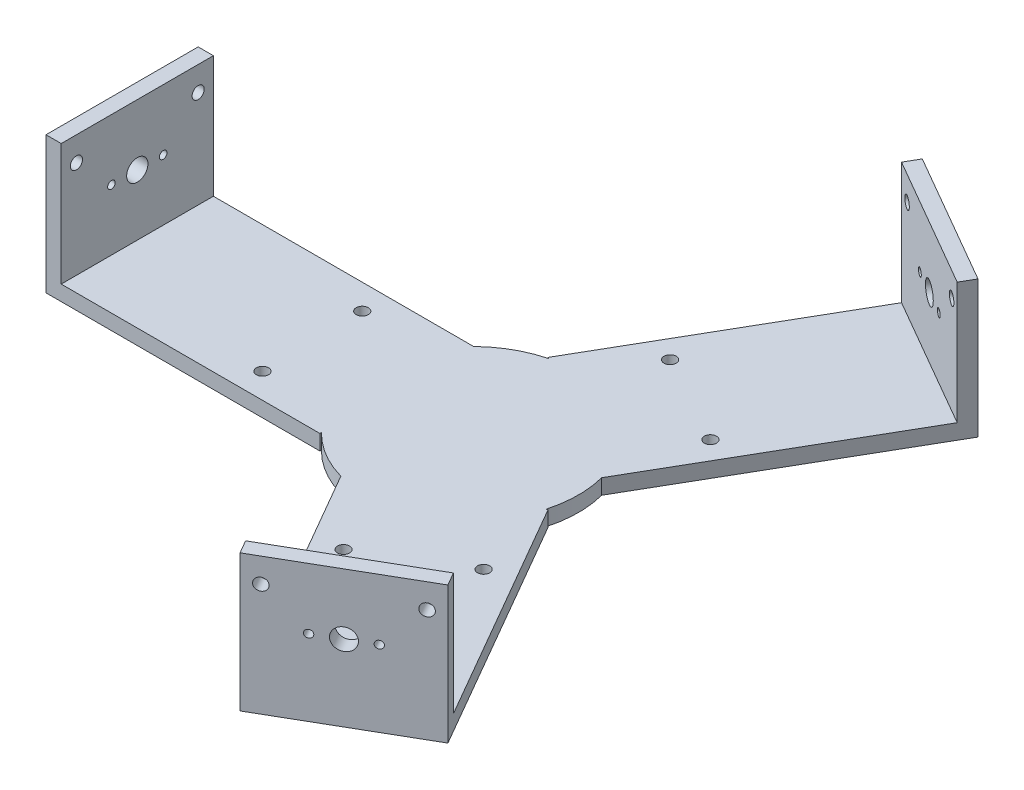
SolidWorks part; units mm, degrees
ref_plane "Plan de face" through (0, 0, 0) normal (0, 0, 1) x (1, 0, 0)
ref_plane "Plan de dessus" through (0, 0, 0) normal (0, 1, 0) x (1, 0, 0)
ref_plane "Plan de droite" through (0, 0, 0) normal (1, 0, 0) x (0, 0, -1)
sketch "Esquisse3" plane through (0, 0, 0) normal (0, 1, 0) x (1, 0, 0)
  line L0 (-150.1573, 0) -> (189.6273, 0) construction
  line L1 (-83.8395, -145.9242) -> (87.7229, 151.2306) construction
  line L2 (-78.0725, 135.2255) -> (117.7517, -203.9519) construction
  line L3 (-125, 131.2995) -> (-125, -153.5705) construction
  line L4 (-25, -25) -> (-115, -25)
  line L6 (-25, 25) -> (-24.4949, 25)
  line L7 (-115, -25) -> (-115, 25)
  line L8 (-25, -25) -> (-115, 25) construction
  line L9 (-25, 25) -> (-115, -25) construction
  line L10 (-24.4949, 25) -> (-115, 25)
  line L11 (33.8981, 8.7132) -> (79.1506, 87.0929)
  line L12 (35.8494, 112.0929) -> (79.1506, 87.0929)
  line L13 (-9.1506, 34.1506) -> (35.8494, 112.0929)
  line L14 (-9.4032, -33.7132) -> (35.8494, -112.0929)
  line L15 (79.1506, -87.0929) -> (35.8494, -112.0929)
  line L16 (34.1506, -9.1506) -> (79.1506, -87.0929)
  line L17 (-24.4949, 25) -> (-25, -25)
  line L18 (-9.1506, 34.1506) -> (33.8981, 8.7132)
  line L19 (-9.4032, -33.7132) -> (34.1506, -9.1506)
  circle A0 centre (0, 0) radius 125
  circle A1 centre (0, 0) radius 35
  circle A2 centre (0, 0) radius 125
  circle A3 centre (0, 0) radius 125
  point P9 (-70, 0)
  point P32 (0, 0)
  dimension "D1" = 250
  dimension "D4" = 70
  dimension "D2" = 120
  dimension "D3" = 120
  dimension "D5" = 10
  dimension "D6" = 50
  dimension "D7" = 90
  dimension "D8" = 3
extrude "Boss.-Extru.3" add sketch "Esquisse3" along normal blind 5 contours A1 L6 L10 L7 L4 L17 | A1 L14 L15 L16 L19 | L19 A1 L18 L17 | A1 L11 L12 L13 L18 | L18 A1 | A1 region at (-73.3157, 0, -0.0007) region at (0, 0, 0) region at (36.6572, 0, 63.4937) region at (14.7041, 0, -24.8843) region at (36.6585, 0, -63.4929)
sketch "Esquisse4" plane through (0, 5, 0) normal (0, 1, 0) x (1, 0, 0)
  line L0 (-25, -25) -> (-115, -25) construction
  line L1 (-115, 25) -> (-110, 25)
  line L2 (-115, 25) -> (-115, -25)
  line L3 (-115, -25) -> (-110, -25)
  line L4 (-110, 25) -> (-110, -25)
  line L5 (35.8494, 112.0929) -> (79.1506, 87.0929)
  line L6 (79.1506, 87.0929) -> (76.6506, 82.7628)
  line L7 (33.8981, 8.7132) -> (79.1506, 87.0929) construction
  line L8 (76.6506, 82.7628) -> (33.3494, 107.7628)
  line L9 (-9.1506, 34.1506) -> (35.8494, 112.0929) construction
  line L10 (33.3494, 107.7628) -> (35.8494, 112.0929)
  line L11 (79.1506, -87.0929) -> (76.6506, -82.7628)
  line L12 (34.1506, -9.1506) -> (79.1506, -87.0929) construction
  line L13 (76.6506, -82.7628) -> (33.3494, -107.7628)
  line L14 (-9.4032, -33.7132) -> (35.8494, -112.0929) construction
  line L15 (33.3494, -107.7628) -> (35.8494, -112.0929)
  line L16 (35.8494, -112.0929) -> (79.1506, -87.0929)
  dimension "D1" = 5
  dimension "D2" = 5
  dimension "D3" = 5
extrude "Boss.-Extru.4" add sketch "Esquisse4" along normal blind 40
sketch "Esquisse5" plane through (-110, 0, 0) normal (1, 0, 0) x (0, 0, -1)
  line L0 (-25, 25) -> (39.5019, 25) construction
  line L1 (-25, 45) -> (-25, 5) construction
  circle A0 centre (0, 25) radius 3.5
  circle A1 centre (-8.5, 25) radius 1.25
  circle A2 centre (8.5, 25) radius 1.25
  dimension "D1" = 7
  dimension "D4" = 2.5
  dimension "D5" = 2.5
  dimension "D2" = 8.5
  dimension "D3" = 8.5
extrude "Enlèv. mat.-Extru.1" cut sketch "Esquisse5" against normal through all
sketch "Esquisse6" plane through (55, 0, 95.2628) normal (-0.5, 0, -0.866) x (-0.866, 0, 0.5)
  line L0 (-25, 25) -> (25, 25) construction
  line L1 (-25, 45) -> (-25, 5) construction
  line L2 (25, 45) -> (25, 5) construction
  circle A0 centre (0, 25) radius 3.5
  circle A1 centre (-8.5, 25) radius 1.25
  circle A2 centre (8.5, 25) radius 1.25
  dimension "D1" = 7
  dimension "D4" = 2.5
  dimension "D5" = 2.5
  dimension "D2" = 8.5
  dimension "D3" = 8.5
extrude "Enlèv. mat.-Extru.2" cut sketch "Esquisse6" against normal through all
sketch "Esquisse7" plane through (55, 0, -95.2628) normal (-0.5, 0, 0.866) x (0.866, 0, 0.5)
  line L0 (-25, 25) -> (25, 25) construction
  line L1 (-25, 45) -> (-25, 5) construction
  line L2 (25, 45) -> (25, 5) construction
  circle A0 centre (0, 25) radius 3.5
  circle A1 centre (8.5, 25) radius 1.25
  circle A2 centre (-8.5, 25) radius 1.25
  dimension "D1" = 7
  dimension "D4" = 2.5
  dimension "D5" = 2.5
  dimension "D2" = 8.5
  dimension "D3" = 8.5
extrude "Enlèv. mat.-Extru.3" cut sketch "Esquisse7" against normal through all
sketch "Esquisse8" plane through (0, 5, 0) normal (0, 1, 0) x (1, 0, 0)
  circle A0 centre (11.9158, -54.1387) radius 2 construction
  circle A1 centre (40.5685, -36.7667) radius 2 construction
  circle A2 centre (11.5566, 53.5167) radius 2 construction
  circle A3 centre (40.9276, 37.3887) radius 2 construction
  circle A4 centre (-52.1251, -16.75) radius 2 construction
  circle A5 centre (-52.8434, 16.75) radius 2 construction
  circle A6 centre (11.9158, -54.1387) radius 2
  circle A7 centre (40.5685, -36.7667) radius 2
  circle A8 centre (11.5566, 53.5167) radius 2
  circle A9 centre (40.9276, 37.3887) radius 2
  circle A10 centre (-52.1251, -16.75) radius 2
  circle A11 centre (-52.8434, 16.75) radius 2
extrude "Enlèv. mat.-Extru.4" cut sketch "Esquisse8" against normal through all
sketch "Esquisse9" plane through (-115, 0, 0) normal (-1, 0, 0) x (0, 0, 1)
  circle A0 centre (-20, 37) radius 2 construction
  circle A1 centre (20, 37) radius 2 construction
  circle A2 centre (-20, 37) radius 2
  circle A3 centre (20, 37) radius 2
sketch "Esquisse10" plane through (57.5, 0, -99.5929) normal (0.5, 0, -0.866) x (-0.866, 0, -0.5)
  circle A0 centre (-20, 37) radius 2 construction
  circle A1 centre (20, 37) radius 2 construction
  circle A2 centre (-20, 37) radius 2
  circle A3 centre (20, 37) radius 2
sketch "Esquisse11" plane through (57.5, 0, 99.5929) normal (0.5, 0, 0.866) x (0.866, 0, -0.5)
  circle A0 centre (20, 37) radius 2 construction
  circle A1 centre (-20, 37) radius 2 construction
  circle A2 centre (20, 37) radius 2
  circle A3 centre (-20, 37) radius 2
extrude "Enlèv. mat.-Extru.5" cut sketch "Esquisse9" against normal through all
extrude "Enlèv. mat.-Extru.6" cut sketch "Esquisse10" against normal through all
extrude "Enlèv. mat.-Extru.7" cut sketch "Esquisse11" against normal up to next
